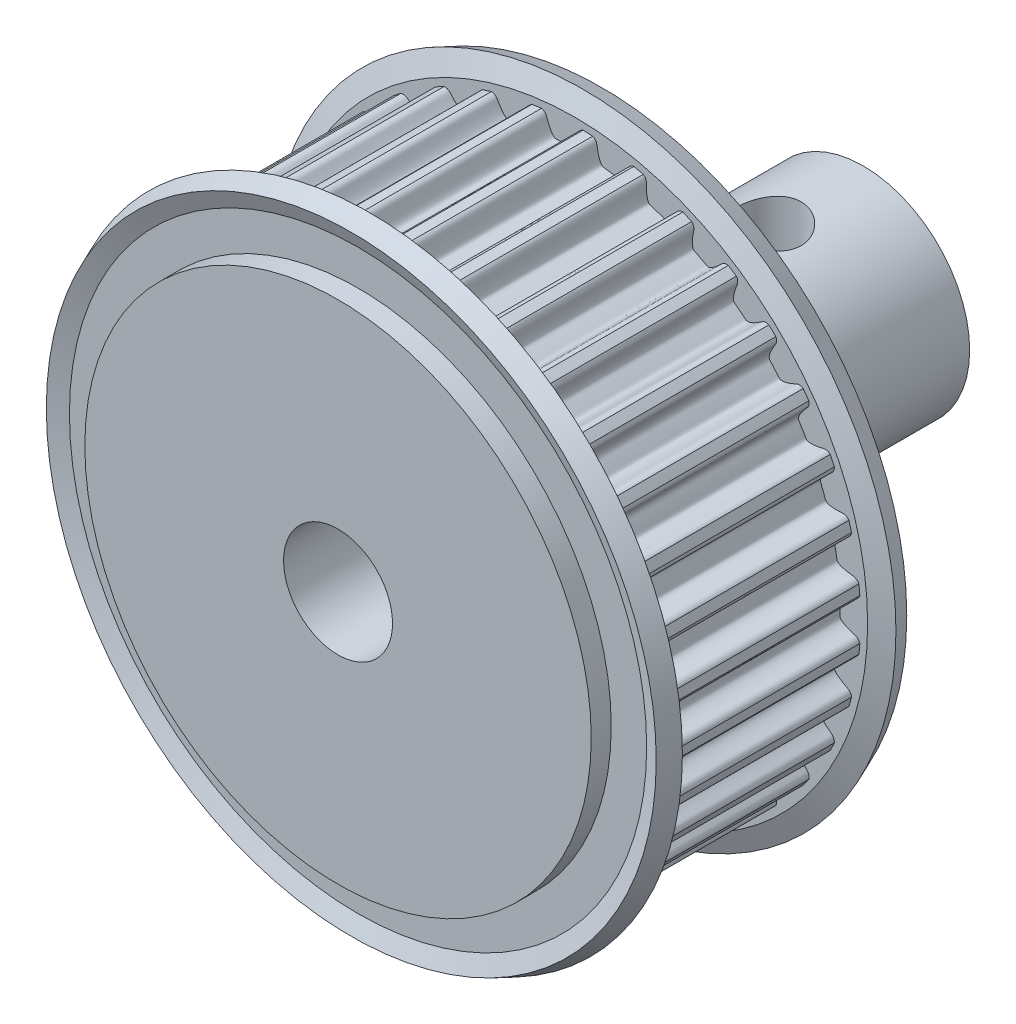
SolidWorks part; units mm, degrees
ref_plane "前视基准面" through (0, 0, 0) normal (0, 0, 1) x (1, 0, 0)
ref_plane "上视基准面" through (0, 0, 0) normal (0, 1, 0) x (1, 0, 0)
ref_plane "右视基准面" through (0, 0, 0) normal (1, 0, 0) x (0, 0, -1)
other "Configuration Table"
ref_axis "基准轴1" through (0, 0, 55) along (0, 0, -1)
sketch "SketchRevolveGearBelt01" plane through (0, 0, 0) normal (1, 0, 0) x (0, 0, -1)
  line L0 (0, 0) -> (1, 0) construction
  line L1 (5.274, 0) -> (5.274, 9.6408)
  line L2 (5.274, 9.6408) -> (4.512, 9.6408)
  line L3 (4.512, 9.6408) -> (4.512, 10.9893)
  line L4 (4.512, 10.9893) -> (4.7696, 11.6112)
  line L5 (4.7696, 11.6112) -> (4.0656, 11.9028)
  line L6 (4.0656, 11.9028) -> (3.75, 11.1408)
  line L7 (3.75, 11.1408) -> (3.75, 10.872)
  line L8 (3.75, 10.872) -> (-3.75, 10.872)
  line L9 (-3.75, 10.872) -> (-3.75, 11.1408)
  line L10 (-3.75, 11.1408) -> (-4.0656, 11.9028)
  line L11 (-4.0656, 11.9028) -> (-4.7696, 11.6112)
  line L12 (-4.7696, 11.6112) -> (-4.512, 10.9893)
  line L13 (-4.512, 10.9893) -> (-4.512, 9.6408)
  line L14 (-4.512, 9.6408) -> (-5.274, 9.6408)
  line L15 (-5.274, 9.6408) -> (-5.274, 0)
  line L16 (-5.274, 0) -> (5.274, 0)
  dimension "GearBeltFlange1OutsideLength" = 1.3484
  dimension "GearBeltFlange1X" = 0.2576
  dimension "GearBeltFlange1Y" = 0.622
  dimension "GearBeltFlangeThickness" = 0.762
  dimension "GearBeltFlangeInside" = 0.2688
  dimension "GearBeltOutsideDiameter" = 10.872
  dimension "GearBeltFlange2X" = 0.2576
revolve "Gates_PowerGrip_GT_2mm, 6mm Belt Width" add sketch "SketchRevolveGearBelt01" angle 360 about L0
sketch "SketchToothGearBelt01" plane through (0, 0, 0) normal (0, 0, 1) x (1, 0, 0)
  arc A0 (10.8521, 0.8621) -> (10.8521, -0.8621) centre (0, 0) cw
  spline S0 degree 3 poles (10.8521, -0.8621) (10.8522, -0.8446) (10.8499, -0.8185) (10.8418, -0.7846) (10.8333, -0.7598) (10.8224, -0.7361) (10.8092, -0.7135) (10.7939, -0.6923) (10.7765, -0.6727) (10.7574, -0.6549) (10.7366, -0.6391) (10.7143, -0.6254) (10.6908, -0.6138) (10.6531, -0.6004) (10.6046, -0.5857) (10.547, -0.5675) (10.4946, -0.5498) (10.4453, -0.5322) (10.3992, -0.5145) (10.3562, -0.4969) (10.3165, -0.4793) (10.2799, -0.4616) (10.2465, -0.444) (10.2162, -0.4264) (10.1891, -0.4087) (10.1652, -0.3911) (10.1444, -0.3735) (10.1268, -0.3558) (10.1123, -0.3381) (10.101, -0.3203) (10.0929, -0.3025) (10.0879, -0.2846) (10.0857, -0.2503) (10.0889, -0.2) (10.089, -0.1333) (10.0898, -0.0667) (10.0899, 0) (10.0898, 0.0667) (10.089, 0.1333) (10.0889, 0.2) (10.0857, 0.2503) (10.0879, 0.2846) (10.0929, 0.3025) (10.101, 0.3203) (10.1123, 0.3381) (10.1268, 0.3558) (10.1444, 0.3735) (10.1652, 0.3911) (10.1891, 0.4087) (10.2162, 0.4264) (10.2465, 0.444) (10.2799, 0.4616) (10.3165, 0.4793) (10.3562, 0.4969) (10.3992, 0.5145) (10.4453, 0.5322) (10.4946, 0.5498) (10.547, 0.5675) (10.6046, 0.5857) (10.6531, 0.6004) (10.6908, 0.6138) (10.7143, 0.6254) (10.7366, 0.6391) (10.7574, 0.6549) (10.7765, 0.6727) (10.7939, 0.6923) (10.8092, 0.7135) (10.8224, 0.7361) (10.8333, 0.7598) (10.8418, 0.7846) (10.8499, 0.8185) (10.8522, 0.8446) (10.8521, 0.8621) knots 0 0 0 0 0.020006 0.030009 0.040012 0.050015 0.060018 0.070022 0.080025 0.090028 0.100031 0.110034 0.120037 0.13004 0.155933 0.178284 0.199479 0.219524 0.238427 0.256199 0.272852 0.288401 0.302863 0.316262 0.328625 0.339989 0.350401 0.35992 0.368626 0.376623 0.384043 0.391052 0.397847 0.423404 0.448936 0.474468 0.5 0.525532 0.551064 0.576596 0.602153 0.608948 0.615957 0.623377 0.631374 0.64008 0.649599 0.660011 0.671375 0.683738 0.697137 0.711599 0.727148 0.743801 0.761573 0.780476 0.800521 0.821716 0.844067 0.86996 0.879963 0.889966 0.899969 0.909972 0.919975 0.929978 0.939982 0.949985 0.959988 0.969991 0.979994 1 1 1 1
extrude "ToothExtrudeCutGearBelt01" cut sketch "SketchToothGearBelt01" against normal blind 3.75 and the other way blind 3.75
pattern_circular "Tooth Pattern, 35" count 35 every 10.286 about axis through (0, 0, 55) along (0, 0, -1) of "ToothExtrudeCutGearBelt01"
sketch "BoreRevolveSketch" plane through (0, 0, 0) normal (1, 0, 0) x (0, 0, -1)
  line L0 (0, 0) -> (1, 0) construction
  line L1 (-5.274, 0) -> (5.274, 0)
  line L2 (5.274, 0) -> (5.274, 5)
  line L3 (5.274, 5) -> (-5.274, 5)
  line L4 (-5.274, 5) -> (-5.274, 0)
  dimension "TaperSide1" = 5
  dimension "TaperSide2" = 5
revolve "BoreRevolveCut" cut sketch "BoreRevolveSketch" angle 360 about L0
sketch "AuxiliarySketchGearBelt01" plane through (0, 0, 0) normal (0, 0, 1) x (1, 0, 0)
  circle A0 centre (0, 0) radius 11.1408 construction
  dimension "PitchDiameter" = 22.2817
sketch "草图5" plane through (0, 0, 5.274) normal (0, 0, 1) x (1, 0, 0)
  circle A0 centre (0, 0) radius 5
extrude "凸台-拉伸1" add sketch "草图5" against normal blind 10
sketch "草图6" plane through (0, 0, -4.726) normal (0, 0, -1) x (-1, 0, 0)
  circle A0 centre (0, 0) radius 2.05
  circle A1 centre (0, 0) radius 4.05
  dimension "D1" = 4.1
  dimension "D2" = 2
extrude "凸台-拉伸2" add sketch "草图6" along normal blind 10
sketch "草图7" plane through (0, 0, -4.726) normal (0, 0, -1) x (-1, 0, 0)
  circle A0 centre (0, 0) radius 2.05
extrude "切除-拉伸2" cut sketch "草图7" against normal blind 10
sketch "草图8" plane through (0, 0, -14.726) normal (0, 0, -1) x (-1, 0, 0)
  line L0 (0, 0) -> (0, 1.5)
  line L1 (-1000, 1.5) -> (49000, 1.5)
  circle A0 centre (0, 0) radius 2.0472
  dimension "D1" = 1.5
extrude "凸台-拉伸3" add sketch "草图8" against normal blind 20 separate body contours L1 A0 region at (0, 1.7216, -14.726)
sketch "草图9" plane through (0, 1.5, 0) normal (0, -1, 0) x (1, 0, 0)
  line L0 (0, 55) -> (0, -55) construction
  circle A0 centre (0, -11.1094) radius 1.25
  dimension "D1" = 2.5
extrude "切除-拉伸6" cut sketch "草图9" against normal through all
sketch "草图10" plane through (0, 0, -14.726) normal (0, 0, -1) x (-1, 0, 0)
  line L1 (0, 0) -> (0, 1.5)
  line L2 (-1.3931, 1.5) -> (1.3931, 1.5) construction
  line L3 (-1000, 1.5) -> (49000, 1.5)
  circle A0 centre (0, 0) radius 2.075
  circle A2 centre (0, 0) radius 2.05
  circle M2 centre (0, 0) radius 2.05
  dimension "D1" = 4.15
  dimension "D2" = 4.1
extrude "切除-拉伸9" cut sketch "草图10" against normal through all contours L3 A0 M2 region at (1.4155, 1.4945, -14.726)
sketch "草图11" plane through (0, 0, 5.274) normal (0, 0, 1) x (1, 0, 0)
  circle A0 centre (0, 0) radius 2.075
extrude "切除-拉伸10" cut sketch "草图11" against normal blind 10
